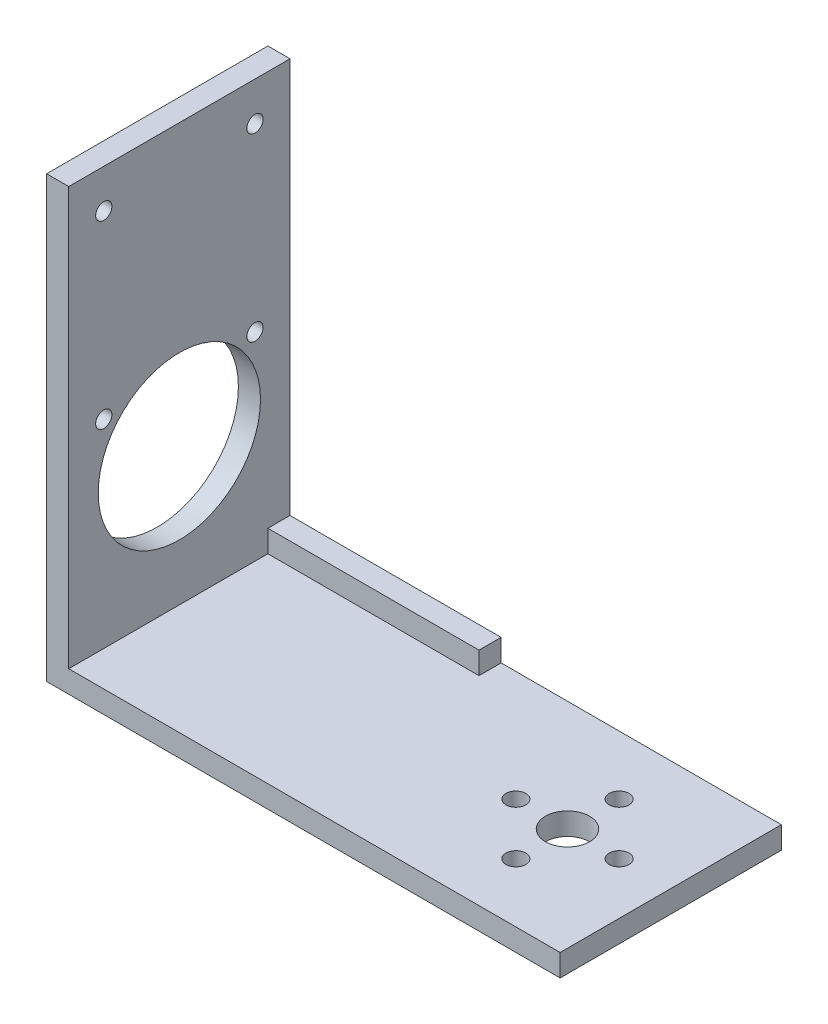
SolidWorks part; units mm, degrees
ref_plane "Front Plane" through (0, 0, 0) normal (0, 0, 1) x (1, 0, 0)
ref_plane "Top Plane" through (0, 0, 0) normal (0, 1, 0) x (1, 0, 0)
ref_plane "Right Plane" through (0, 0, 0) normal (1, 0, 0) x (0, 0, -1)
ref_plane "PZ_m15_000" through (0, 0, -15) normal (0, 0, 1) x (1, 0, 0)
sketch "S_box1" plane through (0, 0, -15) normal (0, 0, 1) x (1, 0, 0)
  line L0 (-55.625, -21.625) -> (14, -21.625)
  line L1 (14, -21.625) -> (14, -18.625)
  line L2 (14, -18.625) -> (-55.625, -18.625)
  line L3 (-55.625, -18.625) -> (-55.625, -21.625)
  dimension "P1" = 55.625
  dimension "P2" = 21.625
  dimension "P3" = 14
  dimension "P4" = 21.625
  dimension "P5" = 14
  dimension "P6" = 18.625
  dimension "P7" = 55.625
  dimension "P8" = 18.625
extrude "Boss_1" add sketch "S_box1" along normal blind 30
sketch "S_box2" plane through (0, 0, -15) normal (0, 0, 1) x (1, 0, 0)
  line L0 (-55.625, -19.125) -> (-52.625, -19.125)
  line L1 (-52.625, -19.125) -> (-52.625, 38)
  line L2 (-52.625, 38) -> (-55.625, 38)
  line L3 (-55.625, 38) -> (-55.625, -19.125)
  dimension "P1" = 55.625
  dimension "P2" = 19.125
  dimension "P3" = 52.625
  dimension "P4" = 19.125
  dimension "P5" = 52.625
  dimension "P6" = 38
  dimension "P7" = 55.625
  dimension "P8" = 38
extrude "Boss_2" add sketch "S_box2" along normal blind 30
sketch "S_box3" plane through (0, 0, -15) normal (0, 0, 1) x (1, 0, 0)
  line L0 (-53.125, -19.125) -> (-24, -19.125)
  line L1 (-24, -19.125) -> (-24, -15.625)
  line L2 (-24, -15.625) -> (-53.125, -15.625)
  line L3 (-53.125, -15.625) -> (-53.125, -19.125)
  dimension "P1" = 53.125
  dimension "P2" = 19.125
  dimension "P3" = 24
  dimension "P4" = 19.125
  dimension "P5" = 24
  dimension "P6" = 15.625
  dimension "P7" = 53.125
  dimension "P8" = 15.625
extrude "Boss_3" add sketch "S_box3" along normal blind 3
ref_plane "PY_m21_725" through (0, -21.725, 0) normal (0, 1, 0) x (1, 0, 0)
sketch "S_hole4" plane through (0, -21.725, 0) normal (0, 1, 0) x (1, 0, 0)
  circle A0 centre (0, 0) radius 3
  dimension "D1_S_hole4" = 6
extrude "Hole_4" cut sketch "S_hole4" along normal blind 3.2
sketch "S_hole5" plane through (0, -21.725, 0) normal (0, 1, 0) x (1, 0, 0)
  circle A0 centre (7, 0) radius 1.35
  dimension "D1_S_hole5" = 2.7
  dimension "P2" = 7
extrude "Hole_5" cut sketch "S_hole5" along normal blind 3.2
sketch "S_hole6" plane through (0, -21.725, 0) normal (0, 1, 0) x (1, 0, 0)
  circle A0 centre (0, -7) radius 1.35
  dimension "D1_S_hole6" = 2.7
  dimension "P2" = 7
extrude "Hole_6" cut sketch "S_hole6" along normal blind 3.2
sketch "S_hole7" plane through (0, -21.725, 0) normal (0, 1, 0) x (1, 0, 0)
  circle A0 centre (-7, 0) radius 1.35
  dimension "D1_S_hole7" = 2.7
  dimension "P2" = 7
extrude "Hole_7" cut sketch "S_hole7" along normal blind 3.2
sketch "S_hole8" plane through (0, -21.725, 0) normal (0, 1, 0) x (1, 0, 0)
  circle A0 centre (0, 7) radius 1.35
  dimension "D1_S_hole8" = 2.7
  dimension "P2" = 7
extrude "Hole_8" cut sketch "S_hole8" along normal blind 3.2
ref_plane "PX_m55_725" through (-55.725, 0, 0) normal (1, 0, 0) x (0, 0, -1)
sketch "S_hole9" plane through (-55.725, 0, 0) normal (1, 0, 0) x (0, 0, -1)
  circle A0 centre (0, 0) radius 11
  dimension "D1_S_hole9" = 22
extrude "Hole_9" cut sketch "S_hole9" along normal blind 3.2
sketch "S_hole10" plane through (-55.725, 0, 0) normal (1, 0, 0) x (0, 0, -1)
  circle A0 centre (10.25, 8.3) radius 1.1
  dimension "D1_S_hole10" = 2.2
  dimension "P2" = 10.25
  dimension "P3" = 8.3
extrude "Hole_10" cut sketch "S_hole10" along normal blind 3.2
sketch "S_hole11" plane through (-55.725, 0, 0) normal (1, 0, 0) x (0, 0, -1)
  circle A0 centre (-10.25, 8.3) radius 1.1
  dimension "D1_S_hole11" = 2.2
  dimension "P2" = 10.25
  dimension "P3" = 8.3
extrude "Hole_11" cut sketch "S_hole11" along normal blind 3.2
sketch "S_hole12" plane through (-55.725, 0, 0) normal (1, 0, 0) x (0, 0, -1)
  circle A0 centre (10.25, 32.75) radius 1.1
  dimension "D1_S_hole12" = 2.2
  dimension "P2" = 10.25
  dimension "P3" = 32.75
extrude "Hole_12" cut sketch "S_hole12" along normal blind 3.2
sketch "S_hole13" plane through (-55.725, 0, 0) normal (1, 0, 0) x (0, 0, -1)
  circle A0 centre (-10.25, 32.75) radius 1.1
  dimension "D1_S_hole13" = 2.2
  dimension "P2" = 10.25
  dimension "P3" = 32.75
extrude "Hole_13" cut sketch "S_hole13" along normal blind 3.2
equation "\"plate_t\" = 3"
equation "\"clearance\" = 0.4"
